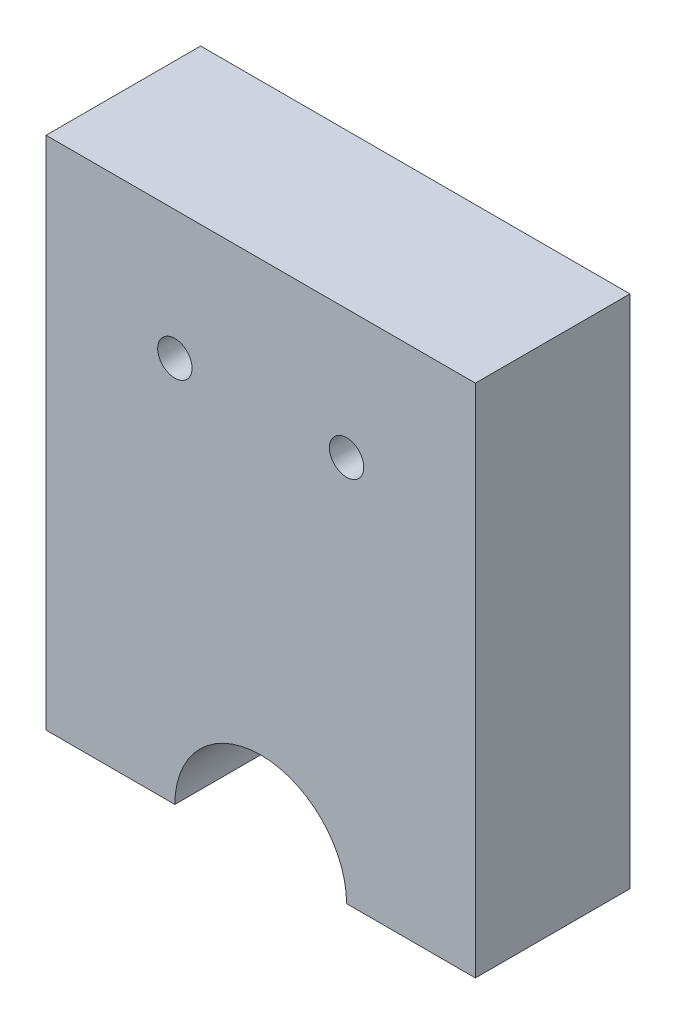
SolidWorks part; units mm, degrees
material "Balsa"
ref_plane "Plan de face" through (0, 0, 0) normal (0, 0, 1) x (1, 0, 0)
ref_plane "Plan de dessus" through (0, 0, 0) normal (0, 1, 0) x (1, 0, 0)
ref_plane "Plan de droite" through (0, 0, 0) normal (1, 0, 0) x (0, 0, -1)
sketch "Sketch1" plane through (0, 0, 0) normal (0, 0, 1) x (1, 0, 0)
  line L1 (0, 0) -> (25, 0)
  line L2 (0, 0) -> (0, 30)
  line L3 (0, 30) -> (25, 30)
  line L4 (25, 0) -> (25, 30)
  dimension "D1" = 30
  dimension "D2" = 25
extrude "Boss-Extrude1" add sketch "Sketch1" along normal blind 9
sketch "Sketch4" plane through (0, 0, 9) normal (0, 0, 1) x (1, 0, 0)
  line L0 (0, 0) -> (25, 0) construction
  line L1 (0, 0) -> (25, 0)
  circle A0 centre (12.5, 0) radius 5
  dimension "D1" = 10
extrude "Cut-Extrude3" cut sketch "Sketch4" against normal through all contours L1 A0 region at (12.5, 2.1221, 9)
sketch "Sketch5" plane through (0, 0, 9) normal (0, 0, 1) x (1, 0, 0)
  line L0 (12.5, 30) -> (12.5, 0) construction
  line L1 (25, 30) -> (0, 30) construction
  line L2 (-4.9885, 22.5) -> (28.5895, 22.5) construction
  circle A0 centre (7.5, 22.5) radius 1
  circle A1 centre (17.5, 22.5) radius 1
  dimension "D2" = 2
  dimension "D1" = 7.5
  dimension "D3" = 5
extrude "Cut-Extrude4" cut sketch "Sketch5" against normal through all
